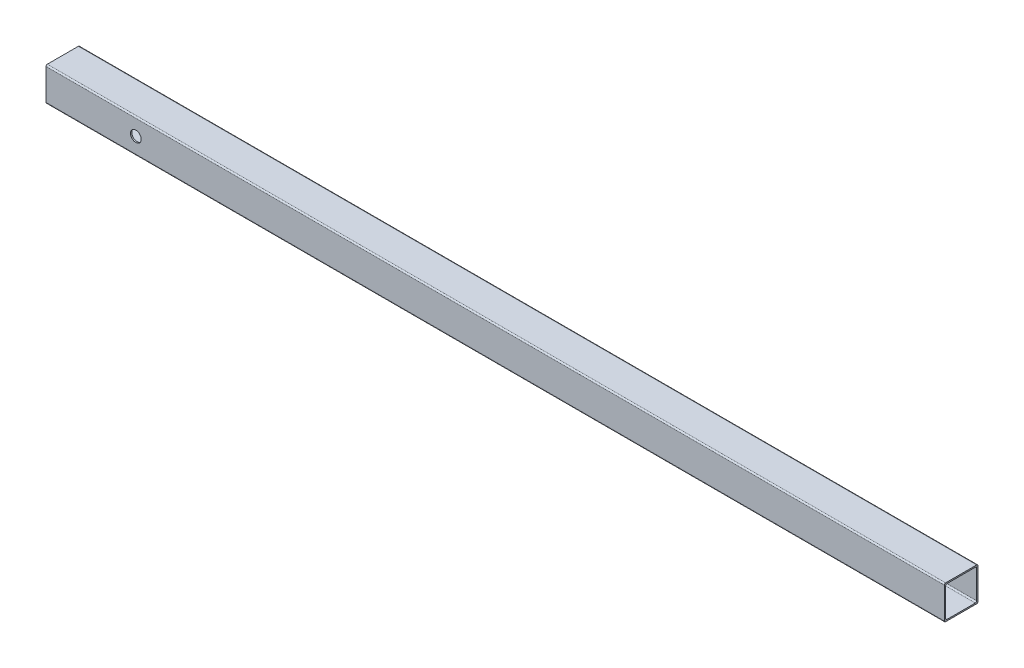
SolidWorks part; units mm, degrees
material "Thornel Mat VMA"
ref_plane "Front Plane" through (0, 0, 0) normal (0, 0, 1) x (1, 0, 0)
ref_plane "Top Plane" through (0, 0, 0) normal (0, 1, 0) x (1, 0, 0)
ref_plane "Right Plane" through (0, 0, 0) normal (1, 0, 0) x (0, 0, -1)
sketch "Sketch2" plane through (0, 0, 0) normal (1, 0, 0) x (0, 0, -1)
  line L1 (0.762, 0) -> (18.288, 0)
  line L2 (0, 0.762) -> (0, 18.288)
  line L3 (0.762, 19.05) -> (18.288, 19.05)
  line L4 (19.05, 0.762) -> (19.05, 18.288)
  line L5 (1.524, 0.762) -> (17.526, 0.762)
  line L6 (0.762, 1.524) -> (0.762, 17.526)
  line L7 (1.524, 18.288) -> (17.526, 18.288)
  line L8 (18.288, 1.524) -> (18.288, 17.526)
  arc A0 (17.526, 18.288) -> (18.288, 17.526) centre (17.526, 17.526) cw
  arc A1 (17.526, 0.762) -> (18.288, 1.524) centre (17.526, 1.524) ccw
  arc A2 (1.524, 0.762) -> (0.762, 1.524) centre (1.524, 1.524) cw
  arc A3 (0.762, 17.526) -> (1.524, 18.288) centre (1.524, 17.526) cw
  arc A4 (18.288, 19.05) -> (19.05, 18.288) centre (18.288, 18.288) cw
  arc A5 (18.288, 0) -> (19.05, 0.762) centre (18.288, 0.762) ccw
  arc A6 (0.762, 0) -> (0, 0.762) centre (0.762, 0.762) cw
  arc A7 (0, 18.288) -> (0.762, 19.05) centre (0.762, 18.288) cw
  point P11 (18.288, 18.288)
  point P14 (18.288, 0.762)
  point P19 (0.762, 18.288)
  point P22 (19.05, 19.05)
  point P25 (19.05, 0)
  point P28 (0, 0)
  point P31 (0, 19.05)
  dimension "D7" = 0.762
  dimension "D1" = 19.05
  dimension "D2" = 19.05
  dimension "D5" = 0.762
  dimension "D6" = 0.762
  dimension "D3" = 0.762
  dimension "D4" = 0.762
extrude "Boss-Extrude1" add sketch "Sketch2" along normal blind 508
sketch "Sketch3" plane through (0, 0, 0) normal (0, 0, 1) x (1, 0, 0)
  line L0 (0, 18.288) -> (0, 0.762) construction
  line L1 (508, 19.05) -> (0, 19.05) construction
  circle A0 centre (50.8, 9.525) radius 3.048
  dimension "D1" = 6.096
  dimension "D2" = 50.8
  dimension "D3" = 9.525
extrude "Cut-Extrude1" cut sketch "Sketch3" against normal up to surface (19.05 mm away) up to face at (254, 9.525, -19.05)
equation "\"shaft\"=0.75"
equation "\"D1@Sketch2\"=\"shaft\""
equation "\"D2@Sketch2\"=\"shaft\""
equation "\"IDshaft\"=0.4375"
equation "\"D3@Sketch3\"=\"shaft\"/2"
